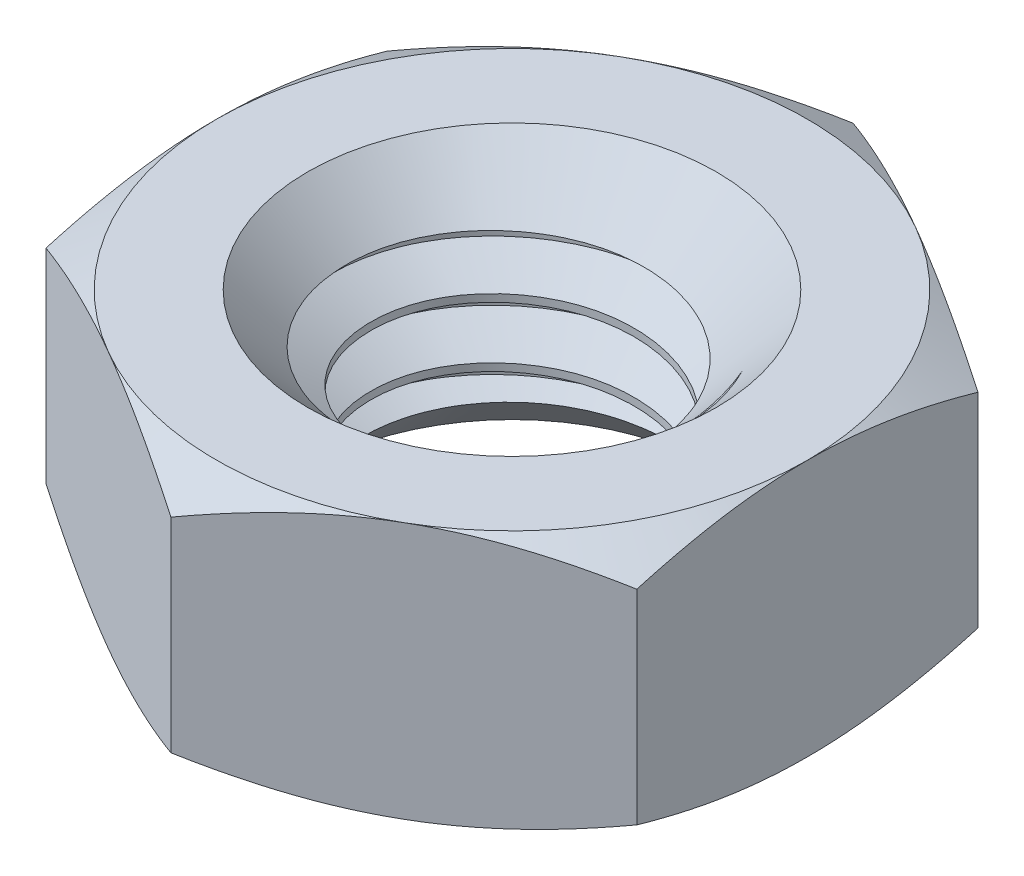
SolidWorks part; units mm, degrees
ref_plane "Front Plane" through (0, 0, 0) normal (0, 0, 1) x (1, 0, 0)
ref_plane "Top Plane" through (0, 0, 0) normal (0, 1, 0) x (1, 0, 0)
ref_plane "Right Plane" through (0, 0, 0) normal (1, 0, 0) x (0, 0, -1)
sketch "Sketch1" plane through (0, 0, 0) normal (0, 1, 0) x (1, 0, 0)
  line L1 (3.45, 1.9919) -> (0, 3.9837) construction
  line L2 (0, 3.9837) -> (-3.45, 1.9919) construction
  line L3 (-3.45, 1.9919) -> (-3.45, -1.9919) construction
  line L4 (-3.45, -1.9919) -> (0, -3.9837) construction
  line L5 (0, -3.9837) -> (3.45, -1.9919) construction
  line L6 (3.45, -1.9919) -> (3.45, 1.9919) construction
  line L7 (0, -1.3) -> (0, -2) construction
  circle A0 centre (0, 0) radius 3.45 construction
  circle A1 centre (0, 0) radius 2 construction
  point P10 (0, -2)
  dimension "Thread Size" = 4
  dimension "Width" = 6.9
  dimension "Thread Pitch" = 0.7
sketch "Sketch9" plane through (0, 0, 0) normal (0, 0, 1) x (1, 0, 0)
  line L0 (0, 1.5) -> (0, -1.5) construction
  dimension "Height" = 3
sketch "Sketch2" plane through (0, 0, 0) normal (0, 1, 0) x (1, 0, 0)
  line L0 (-3.45, -1.9919) -> (0, -3.9837) construction
  line L1 (0, -3.9837) -> (3.45, -1.9919) construction
  line L2 (3.45, -1.9919) -> (3.45, 1.9919) construction
  line L3 (3.45, 1.9919) -> (0, 3.9837) construction
  line L4 (0, 3.9837) -> (-3.45, 1.9919) construction
  line L5 (-3.45, 1.9919) -> (-3.45, -1.9919) construction
  line L6 (-3.45, -1.9919) -> (0, -3.9837)
  line L7 (0, -3.9837) -> (3.45, -1.9919)
  line L8 (3.45, -1.9919) -> (3.45, 1.9919)
  line L9 (3.45, 1.9919) -> (0, 3.9837)
  line L10 (0, 3.9837) -> (-3.45, 1.9919)
  line L11 (-3.45, 1.9919) -> (-3.45, -1.9919)
  circle A0 centre (0, 0) radius 2 construction
  circle A1 centre (0, 0) radius 2
extrude "Boss-Extrude1" add sketch "Sketch2" along normal mid plane 3
sketch "Sketch3" plane through (0, 1.5, 0) normal (0, 1, 0) x (1, 0, 0)
  circle A2 centre (0, 0) radius 3.45 construction
  circle A3 centre (0, 0) radius 3.45
extrude "Cut-Extrude1" cut sketch "Sketch3" against normal through all draft 60 flip side to cut
mirror "Mirror1" about plane through (0, 0, 0) normal (0, 1, 0) of "Cut-Extrude1"
chamfer "Chamfer1" distance 0.385 angle 45 2 edges at (0, -1.5, 2) (0, 1.5, 2)
sketch "Sketch4" plane through (0, 1.5, 0) normal (0, 1, 0) x (1, 0, 0)
  circle A2 centre (0, 0) radius 2 construction
  circle A3 centre (0, 0) radius 2
curve "Helix/Spiral1" pitch 0.7 height 3.7 radius 2 centre (0, 1.5, 0) axis (0, -1, 0) start towards (0, 0, 1)
sketch "Sketch5" plane through (0, 0, 0) normal (0, 0, 1) x (1, 0, 0)
  line L4 (-2.0758, 1.4563) -> (-1.4696, 1.8063) construction
  line L5 (-1.4696, 1.8063) -> (-2.0758, 2.1563) construction
  line L6 (-2.0758, 2.1563) -> (-2.0758, 1.4563) construction
  line L7 (-2, 1.5) -> (-2, 2.1125) construction
  line L8 (-2.0758, 1.8063) -> (-2, 1.8063) construction
  line L9 (-2, 1.8063) -> (-1.5453, 1.8063) construction
  line L10 (-1.5453, 1.8063) -> (-1.4696, 1.8063) construction
  line L11 (-1.5453, 1.7625) -> (-1.5453, 1.85)
  line L12 (-2.0379, 1.4781) -> (-2.0379, 2.1344)
  line L13 (-1.5453, 1.85) -> (-2.0379, 2.1344)
  line L14 (-1.5453, 1.7625) -> (-2.0379, 1.4781)
  point P13 (-2.0379, 1.8063)
  dimension "D1" = 0.7
  dimension "D2" = 0.0875
sweep "Sweep1" add profiles "Sketch5" path "Helix/Spiral1"
sketch "Sketch6" plane through (0, 1.5, 0) normal (0, 1, 0) x (1, 0, 0)
  circle A0 centre (0, 0) radius 2.385 construction
  circle A3 centre (0, 0) radius 2.385
extrude "Cut-Extrude2" cut sketch "Sketch6" along normal through all and the other way blind 10 draft 45
sketch "Sketch10" plane through (0, -1.5, 0) normal (0, -1, 0) x (1, 0, 0)
  circle A1 centre (0, 0) radius 2.385
  circle A2 centre (0, 0) radius 2.385
  dimension "D1" = 0
extrude "Cut-Extrude3" cut sketch "Sketch10" against normal through all draft 45 and the other way through all
equation "\"D1@Boss-Extrude1\" = \"Height@Sketch9\""
equation "\"D3@Helix/Spiral1\"= \"Height@Sketch9\" + \"Thread Pitch@Sketch1\""
equation "\"D4@Helix/Spiral1\" = \"Thread Pitch@Sketch1\""
equation "\"D2@Sketch5\"=\"D1@Sketch5\"/8"
equation "\"D1@Sketch5\"=\"Thread Pitch@Sketch1\""
equation "\"D1@Chamfer1\"=\"Thread Pitch@Sketch1\"*0.55"
